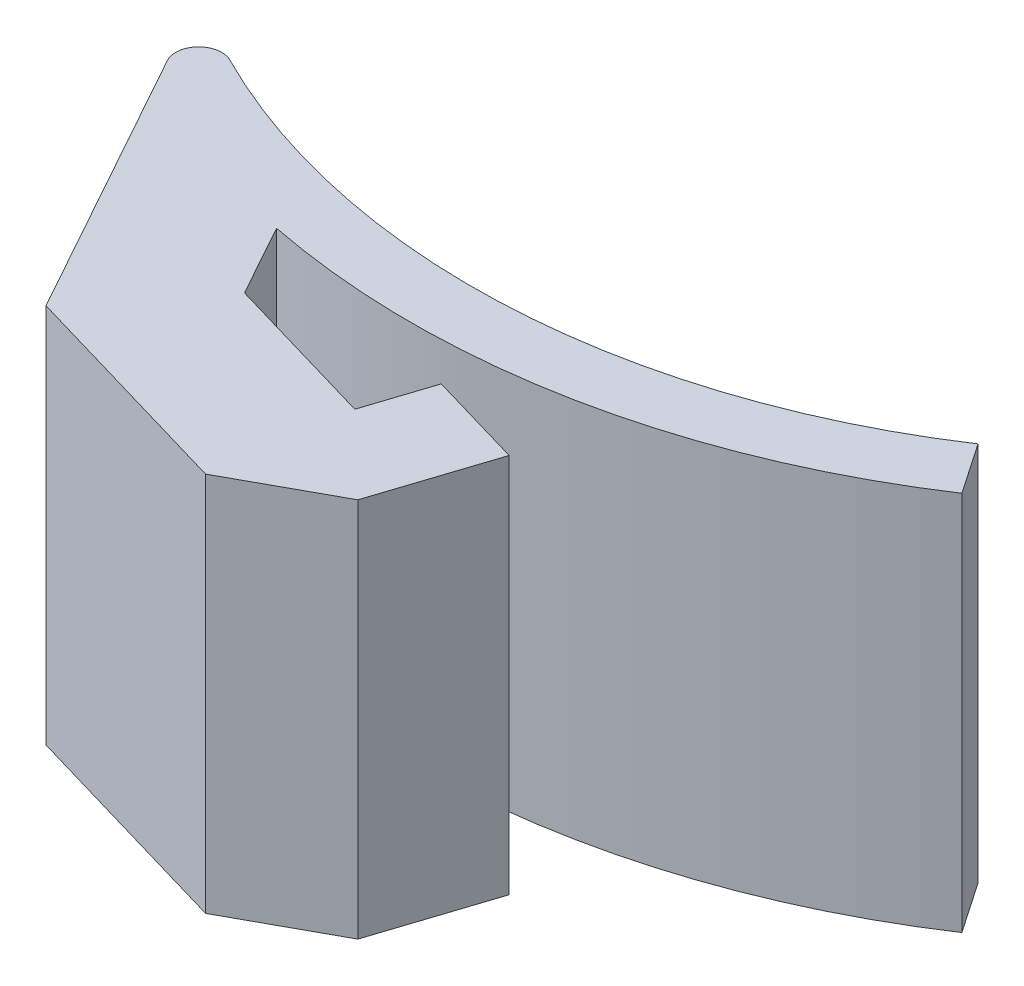
SolidWorks part; units mm, degrees
ref_plane "Спереди" through (0, 0, 0) normal (0, 0, 1) x (1, 0, 0)
ref_plane "Сверху" through (0, 0, 0) normal (0, 1, 0) x (1, 0, 0)
ref_plane "Справа" through (0, 0, 0) normal (1, 0, 0) x (0, 0, -1)
sketch "Эскиз1" plane through (0, 0, 0) normal (0, 1, 0) x (1, 0, 0)
  line L0 (4.2452, -5.0108) -> (4.7271, -3.3642) construction
  line L1 (2.5, -4.5) -> (6.3951, -5.64)
  line L2 (6.3951, -5.64) -> (7.2, -3.175)
  line L3 (7.2, -3.175) -> (5.9523, -2.8099)
  line L4 (5.9523, -2.8099) -> (5.6754, -3.658)
  line L5 (5.6754, -3.658) -> (3.6472, -3.0644)
  line L6 (3.6472, -3.0644) -> (3.1268, -2.1278)
  line L7 (10.12, 0.0055) -> (10.5711, -0.6553)
  line L9 (0.5267, -0.9481) -> (2.5, -4.5)
  line L10 (2.1224, -3.8203) -> (3.5998, -2.9995) construction
  arc A0 (0.9239, -0.5345) -> (10.12, 0.0055) centre (5.0558, 7.6737) ccw
  arc A1 (3.1268, -2.1278) -> (10.5711, -0.6553) centre (5.0558, 7.6737) ccw
  arc A3 (-0.4009, -0.6938) -> (10.5609, -0.6621) centre (5.0558, 7.6737) ccw construction
  arc A4 (0.0361, -0.0237) -> (10.12, 0.0055) centre (5.0558, 7.6737) ccw construction
  arc A5 (0.9239, -0.5345) -> (0.5267, -0.9481) centre (0.789, -0.8024) ccw
  point P12 (3.1251, -2.9116)
  point P14 (3.6084, -2.9947)
  point P18 (5.5945, -1.5)
  point P25 (4.7228, -3.3792)
  point P26 (0, 0)
  dimension "D8" = 0.3
  dimension "D1" = 10.12
  dimension "D2" = 1.7
  dimension "D3" = 4.5
  dimension "D4" = 2.5
  dimension "D5" = 7.2
  dimension "D6" = 5.64
  dimension "D7" = 1.3
  dimension "D9" = 1.7
  dimension "D11" = 1.5
  dimension "D12" = 0.8
extrude "Бобышка-Вытянуть1" add sketch "Эскиз1" along normal blind 4.95
chamfer "Фаска1" distance 1 angle 45 1 edges at (6.3951, 2.475, 5.64) first distance on face at (4.4475, 2.475, 5.07)
